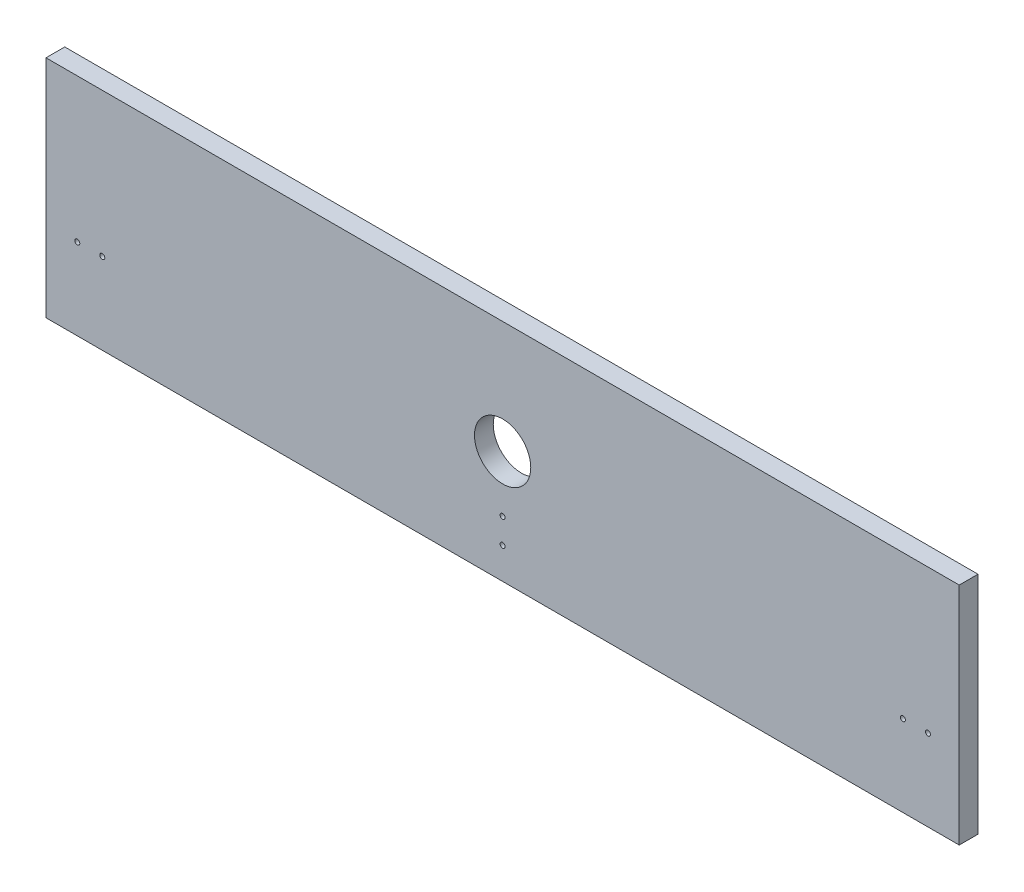
SolidWorks part; units mm, degrees
ref_plane "Alzado" through (0, 0, 0) normal (0, 0, 1) x (1, 0, 0)
ref_plane "Planta" through (0, 0, 0) normal (0, 1, 0) x (1, 0, 0)
ref_plane "Vista lateral" through (0, 0, 0) normal (1, 0, 0) x (0, 0, -1)
sketch "Croquis1" plane through (0, 0, 0) normal (0, 0, 1) x (1, 0, 0)
  line L1 (-365, -90) -> (365, -90)
  line L2 (-365, -90) -> (-365, 90)
  line L3 (-365, 90) -> (365, 90)
  line L4 (365, -90) -> (365, 90)
  line L5 (-365, -90) -> (365, 90) construction
  line L6 (-365, 90) -> (365, -90) construction
  point P0 (0, 0)
extrude "Saliente-Extruir1" add sketch "Croquis1" along normal blind 15
sketch "Croquis2" plane through (0, 0, 15) normal (0, 0, 1) x (1, 0, 0)
  line L0 (-365, -90) -> (365, -90) construction
  line L1 (-365, 90) -> (-365, -90) construction
  line L2 (365, -90) -> (365, 90) construction
  circle A0 centre (-340, -25) radius 2
  circle A1 centre (0, -65) radius 2
  circle A2 centre (0, -45) radius 2
  circle A3 centre (-320, -25) radius 2
  circle A4 centre (340, -25) radius 2
  circle A5 centre (320, -25) radius 2
  point P7 (0, -90)
  dimension "D1" = 25
  dimension "D3" = 25
  dimension "D7" = 25
  dimension "D2" = 20
  dimension "D4" = 20
  dimension "D5" = 65
  dimension "D6" = 0
  dimension "D8" = 20
  dimension "D9" = 65
extrude "Cortar-Extruir1" cut sketch "Croquis2" against normal blind 10
sketch "Croquis3" plane through (0, 0, 15) normal (0, 0, 1) x (1, 0, 0)
  circle A0 centre (0, 0) radius 22.5
extrude "Cortar-Extruir2" cut sketch "Croquis3" against normal up to surface (15 mm away) up to face at (0, 0, 0)
